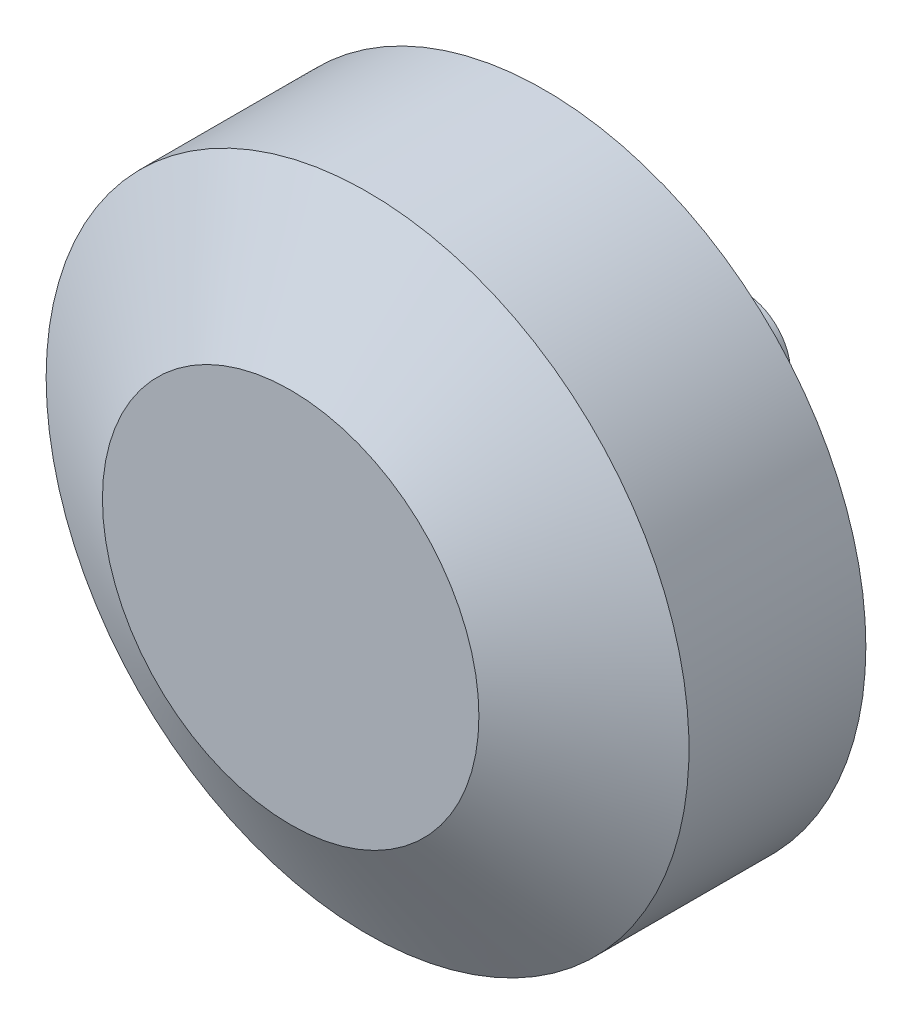
SolidWorks part; units mm, degrees
ref_plane "Piano frontale" through (0, 0, 0) normal (0, 0, 1) x (1, 0, 0)
ref_plane "Piano superiore" through (0, 0, 0) normal (0, 1, 0) x (1, 0, 0)
ref_plane "Piano destro" through (0, 0, 0) normal (1, 0, 0) x (0, 0, -1)
sketch "Schizzo2" plane through (0, 0, 0) normal (0, 0, 1) x (1, 0, 0)
  circle A0 centre (0, 0) radius 20.9
  dimension "D1" = 41.8
extrude "Estrusione-Estrusione1" add sketch "Schizzo2" along normal mid plane 21.5 contours A0
sketch "Schizzo3" plane through (0, 0, -10.75) normal (0, 0, -1) x (-1, 0, 0)
  circle A0 centre (0, 0) radius 3
  dimension "D1" = 6
extrude "Estrusione-Estrusione2" add sketch "Schizzo3" along normal blind 8
chamfer "Smusso1" distance 5 angle 60 2 edges at (20.9, 0, 10.75) (20.9, 0, -10.75) first distance on face at (20.9, 0, 10.75)
ref_axis "Assi1" through (0, 0, -18.75) along (0, 0, 1)
